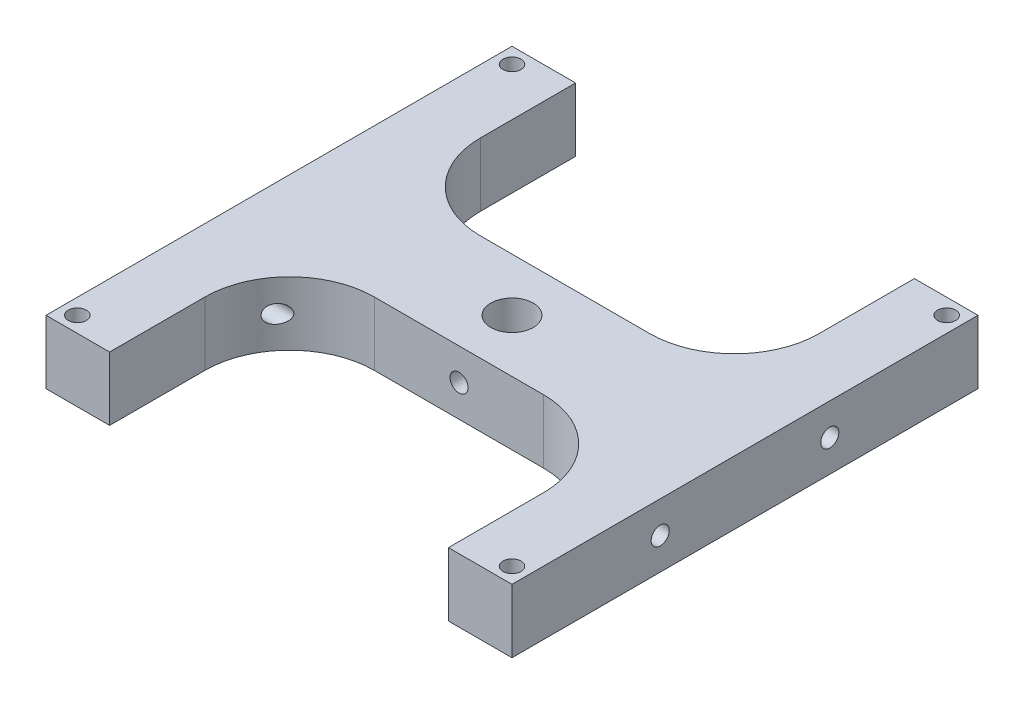
SolidWorks part; units mm, degrees
material "6061-T6 (SS)"
ref_plane "Front Plane" through (0, 0, 0) normal (0, 0, 1) x (1, 0, 0)
ref_plane "Top Plane" through (0, 0, 0) normal (0, 1, 0) x (1, 0, 0)
ref_plane "Right Plane" through (0, 0, 0) normal (1, 0, 0) x (0, 0, -1)
sketch "Sketch1" plane through (0, 0, 0) normal (0, 1, 0) x (1, 0, 0)
  line L1 (-38.1, -38.1) -> (38.1, -38.1)
  line L2 (-38.1, -38.1) -> (-38.1, 38.1)
  line L3 (-38.1, 38.1) -> (38.1, 38.1)
  line L4 (38.1, -38.1) -> (38.1, 38.1)
  line L5 (-38.1, -38.1) -> (38.1, 38.1) construction
  line L6 (-38.1, 38.1) -> (38.1, -38.1) construction
  point P0 (0, 0)
  dimension "D1" = 76.2
  dimension "D2" = 76.2
extrude "Boss-Extrude1" add sketch "Sketch1" along normal blind 3.175
sketch "Sketch2" plane through (0, 3.175, 0) normal (0, 1, 0) x (1, 0, 0)
  line L0 (-38.1, 38.1) -> (-38.1, -38.1) construction
  line L1 (34.8971, -34.8971) -> (-34.8971, -34.8971)
  line L2 (34.8971, -34.8971) -> (34.8971, 34.8971)
  line L3 (34.8971, 34.8971) -> (-34.8971, 34.8971)
  line L4 (-34.8971, -34.8971) -> (-34.8971, 34.8971)
  line L5 (38.1, -38.1) -> (38.1, 38.1) construction
  line L6 (-38.1, -38.1) -> (38.1, -38.1) construction
  line L14 (38.1, 38.1) -> (-38.1, 38.1) construction
  point P0 (0, 0)
  point P6 (0, 0)
  dimension "D1" = 3.2029
  dimension "D2" = 3.2029
  dimension "D3" = 3.2029
  dimension "D4" = 3.2029
extrude "Boss-Extrude2" add sketch "Sketch2" along normal blind 9.525
sketch "Sketch8" plane through (34.8971, 0, 0) normal (1, 0, 0) x (0, 0, -1)
  line L0 (-38.1, 3.175) -> (38.1, 3.175) construction
  point P0 (-12.7, 7.9375)
  dimension "D1" = 4.7625
  dimension "D2" = 12.7
hole_wizard "#6-32 Tapped Hole3" positions "Sketch10" profile "Sketch9" tap size "#6-32" standard "ANSI Inch"
sketch "Sketch10" plane through (34.8971, 0, 0) normal (1, 0, 0) x (0, 0, -1)
  point P0 (-12.7, 7.9375)
sketch "Sketch9" plane through (34.8971, 7.9375, 12.7) normal (0, 1, 0) x (0, 0, -1)
  line L0 (0, 0) -> (0, 11.9887)
  line L1 (0, 11.9887) -> (1.3525, 11.176)
  line L2 (1.3525, 11.176) -> (1.3525, 0)
  line L5 (1.3525, 0) -> (0, 0)
  line L10 (0, 11.9887) -> (-1.3526, 11.176) construction
  line L11 (0, -6.35) -> (0, 107.95) construction
  dimension "Tap Drill Dia." = 2.7051
  dimension "Tap Drill Depth" = 11.176
  dimension "Drill Angle" = 118
cosmetic thread "Hole Thread1" parameters "D1"=7.112, "D2"=3.5052
mirror "Mirror1" about plane through (0, 0, 0) normal (0, 0, 1) of "#6-32 Tapped Hole3"
mirror "Mirror2" about plane through (0, 0, 0) normal (1, 0, 0) of "Mirror1"
sketch "Sketch11" plane through (0, 0, 0) normal (0, -1, 0) x (1, 0, 0)
  circle A0 centre (32.5501, -32.5501) radius 2.032
  dimension "D1" = 4.064
hole_wizard "#6-32 Tapped Hole1" positions "Sketch13" profile "Sketch12" tap size "#6-32" standard "ANSI Inch" end condition through all
sketch "Sketch13" plane through (0, 0, 0) normal (0, -1, 0) x (-1, 0, 0)
  point P0 (-32.5501, 32.5501)
sketch "Sketch12" plane through (32.5501, 0, -32.5501) normal (1, 0, 0) x (0, 0, -1)
  line L0 (0, 0) -> (0, 12.7)
  line L1 (0, 12.7) -> (1.3525, 12.7)
  line L2 (1.3525, 12.7) -> (1.3525, 0)
  line L5 (1.3525, 0) -> (0, 0)
  line L11 (0, -6.35) -> (0, 107.95) construction
  dimension "Thru Tap Drill Dia." = 2.7051
  dimension "Thru Tap Drill Depth" = 12.7
cosmetic thread "Hole Thread2" parameters "D2"=3.5052
ref_axis "Axis1" through (0, -0.635, 0) along (0, 1, 0)
pattern_circular "CirPattern1" count 4 over 360 about axis through (0, -0.635, 0) along (0, 1, 0) of "#6-32 Tapped Hole1"
sketch "Sketch14" plane through (0, 0, 0) normal (0, -1, 0) x (1, 0, 0)
  circle A0 centre (0, 0) radius 3.175
  dimension "D1" = 6.35
extrude "Cut-Extrude1" cut sketch "Sketch14" against normal through all
sketch "Sketch15" plane through (0, 12.7, 0) normal (0, 1, 0) x (1, 0, 0)
  line L0 (-25.3721, -7.9375) -> (25.3721, -7.9375)
  line L1 (25.3721, -7.9375) -> (25.3721, -34.8971)
  line L2 (-34.8971, -34.8971) -> (34.8971, -34.8971) construction
  line L3 (-25.3721, -7.9375) -> (-25.3721, -34.8971)
  line L4 (-34.8971, 34.8971) -> (-34.8971, -34.8971) construction
  line L5 (34.8971, -34.8971) -> (34.8971, 34.8971) construction
  line L6 (-25.3721, -34.8971) -> (25.3721, -34.8971)
  dimension "D1" = 9.525
  dimension "D2" = 9.525
  dimension "D3" = 7.9375
extrude "Cut-Extrude2" cut sketch "Sketch15" against normal blind 9.525
fillet "Fillet1" radius 12.7 2 edges at (25.3721, 7.9375, 7.9375) (-25.3721, 7.9375, 7.9375)
sketch "Sketch16" plane through (0, 0, 7.9375) normal (0, 0, 1) x (1, 0, 0)
  line L0 (12.6721, 3.175) -> (-12.6721, 3.175) construction
  point P0 (0, 7.9375)
  dimension "D1" = 4.7625
hole_wizard "#6-32 Tapped Hole2" positions "Sketch18" profile "Sketch17" tap size "#6-32" standard "ANSI Inch"
sketch "Sketch18" plane through (0, 0, 7.9375) normal (0, 0, 1) x (1, 0, 0)
  point P0 (0, 7.9375)
sketch "Sketch17" plane through (0, 7.9375, 7.9375) normal (1, 0, 0) x (0, -1, 0)
  line L0 (0, 0) -> (0, 10.4647)
  line L1 (0, 10.4647) -> (1.3525, 9.652)
  line L2 (1.3525, 9.652) -> (1.3525, 0)
  line L5 (1.3525, 0) -> (0, 0)
  line L10 (0, 10.4647) -> (-1.3526, 9.652) construction
  line L11 (0, -6.35) -> (0, 107.95) construction
  dimension "Tap Drill Dia." = 2.7051
  dimension "Tap Drill Depth" = 9.652
  dimension "Drill Angle" = 118
cosmetic thread "Hole Thread3" parameters "D1"=5.065, "D2"=3.5052
mirror "Mirror3" about plane through (0, 0, 0) normal (0, 0, 1) of "Cut-Extrude2", "Fillet1"
sketch "Sketch21" plane through (0, 0, 0) normal (0, -1, 0) x (1, 0, 0)
  line L4 (38.1, -38.1) -> (38.1, 38.1)
  line L5 (38.1, 38.1) -> (-38.1, 38.1)
  line L6 (-38.1, 38.1) -> (-38.1, -38.1)
  line L7 (-38.1, -38.1) -> (38.1, -38.1)
  line L8 (38.1, -38.1) -> (38.1, 38.1)
  line L9 (38.1, 38.1) -> (-38.1, 38.1)
  line L10 (-38.1, 38.1) -> (-38.1, -38.1)
  line L11 (-38.1, -38.1) -> (38.1, -38.1)
  dimension "D1" = 0
extrude "Cut-Extrude3" cut sketch "Sketch21" against normal blind 3.175
equation "\"D2@Sketch2\"=\"D1@Sketch2\""
equation "\"D2@Sketch1\"=\"D1@Sketch1\""
equation "\"D3@Sketch2\"=\"D2@Sketch2\""
equation "\"D4@Sketch2\"=\"D2@Sketch2\""
equation "\"D2@Sketch15\"=\"D1@Sketch15\""
